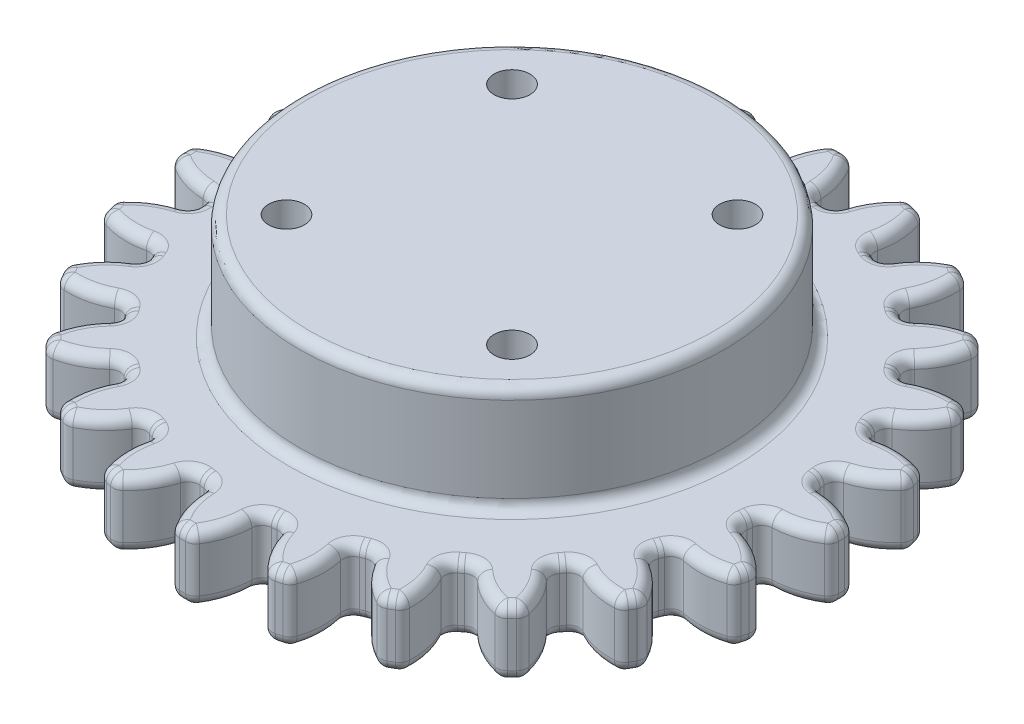
SolidWorks part; units mm, degrees
ref_plane "Front Plane" through (0, 0, 0) normal (0, 0, 1) x (1, 0, 0)
ref_plane "Top Plane" through (0, 0, 0) normal (0, 1, 0) x (1, 0, 0)
ref_plane "Right Plane" through (0, 0, 0) normal (1, 0, 0) x (0, 0, -1)
sketch "Sketch2" plane through (0, 0, 0) normal (0, 1, 0) x (1, 0, 0)
  line L0 (1.6066, 22.8619) -> (0, 0) construction
  line L1 (1.6066, 22.8619) -> (6.4656, 5.8944) construction
  line L2 (-1.8126, 20.7187) -> (0, 0) construction
  line L3 (0, 0) -> (1.8126, 20.7187) construction
  line L4 (-3.6115, 20.4818) -> (0, 0) construction
  line L5 (-6.4181, 23.9528) -> (0, 0) construction
  circle A0 centre (0, 0) radius 20.7978 construction
  circle A1 centre (0, 0) radius 24.7978 construction
  arc A2 (1.8126, 20.7187) -> (0.6469, 24.7894) centre (-4.078, 21.234) ccw
  arc A3 (-1.8126, 20.7187) -> (-0.6469, 24.7894) centre (4.078, 21.234) cw
  arc A4 (0.6469, 24.7894) -> (-0.6469, 24.7894) centre (0, 0) ccw
  arc A5 (1.8126, 20.7187) -> (3.6115, 20.4818) centre (0, 0) cw
  arc A6 (3.6115, 20.4818) -> (5.7911, 24.1121) centre (9.4348, 19.455) cw
  arc A7 (7.0408, 23.7772) -> (5.7911, 24.1121) centre (0, 0) ccw
  arc A8 (7.1133, 19.5435) -> (7.0408, 23.7772) centre (1.5567, 21.566) ccw
  arc A9 (7.1133, 19.5435) -> (8.7895, 18.8492) centre (0, 0) cw
  arc A10 (8.7895, 18.8492) -> (11.8344, 21.7917) centre (14.1487, 16.3502) cw
  arc A11 (12.9549, 21.1447) -> (11.8344, 21.7917) centre (0, 0) ccw
  arc A12 (11.9291, 17.0366) -> (12.9549, 21.1447) centre (7.0854, 20.4282) ccw
  arc A13 (11.9291, 17.0366) -> (13.3686, 15.932) centre (0, 0) cw
  arc A14 (13.3686, 15.932) -> (17.0713, 17.9862) centre (17.8983, 12.1311) cw
  arc A15 (17.9862, 17.0713) -> (17.0713, 17.9862) centre (0, 0) ccw
  arc A16 (15.932, 13.3686) -> (17.9862, 17.0713) centre (12.1311, 17.8983) ccw
  arc A17 (15.932, 13.3686) -> (17.0366, 11.9291) centre (0, 0) cw
  arc A18 (17.0366, 11.9291) -> (21.1447, 12.9549) centre (20.4282, 7.0854) cw
  arc A19 (21.7917, 11.8344) -> (21.1447, 12.9549) centre (0, 0) ccw
  arc A20 (18.8492, 8.7895) -> (21.7917, 11.8344) centre (16.3502, 14.1487) ccw
  arc A21 (18.8492, 8.7895) -> (19.5435, 7.1133) centre (0, 0) cw
  arc A22 (19.5435, 7.1133) -> (23.7772, 7.0408) centre (21.566, 1.5567) cw
  arc A23 (24.1121, 5.7911) -> (23.7772, 7.0408) centre (0, 0) ccw
  arc A24 (20.4818, 3.6115) -> (24.1121, 5.7911) centre (19.455, 9.4348) ccw
  arc A25 (20.4818, 3.6115) -> (20.7187, 1.8126) centre (0, 0) cw
  arc A26 (20.7187, 1.8126) -> (24.7894, 0.6469) centre (21.234, -4.078) cw
  arc A27 (24.7894, -0.6469) -> (24.7894, 0.6469) centre (0, 0) ccw
  arc A28 (20.7187, -1.8126) -> (24.7894, -0.6469) centre (21.234, 4.078) ccw
  arc A29 (20.7187, -1.8126) -> (20.4818, -3.6115) centre (0, 0) cw
  arc A30 (20.4818, -3.6115) -> (24.1121, -5.7911) centre (19.455, -9.4348) cw
  arc A31 (23.7772, -7.0408) -> (24.1121, -5.7911) centre (0, 0) ccw
  arc A32 (19.5435, -7.1133) -> (23.7772, -7.0408) centre (21.566, -1.5567) ccw
  arc A33 (19.5435, -7.1133) -> (18.8492, -8.7895) centre (0, 0) cw
  arc A34 (18.8492, -8.7895) -> (21.7917, -11.8344) centre (16.3502, -14.1487) cw
  arc A35 (21.1447, -12.9549) -> (21.7917, -11.8344) centre (0, 0) ccw
  arc A36 (17.0366, -11.9291) -> (21.1447, -12.9549) centre (20.4282, -7.0854) ccw
  arc A37 (17.0366, -11.9291) -> (15.932, -13.3686) centre (0, 0) cw
  arc A38 (15.932, -13.3686) -> (17.9862, -17.0713) centre (12.1311, -17.8983) cw
  arc A39 (17.0713, -17.9862) -> (17.9862, -17.0713) centre (0, 0) ccw
  arc A40 (13.3686, -15.932) -> (17.0713, -17.9862) centre (17.8983, -12.1311) ccw
  arc A41 (13.3686, -15.932) -> (11.9291, -17.0366) centre (0, 0) cw
  arc A42 (11.9291, -17.0366) -> (12.9549, -21.1447) centre (7.0854, -20.4282) cw
  arc A43 (11.8344, -21.7917) -> (12.9549, -21.1447) centre (0, 0) ccw
  arc A44 (8.7895, -18.8492) -> (11.8344, -21.7917) centre (14.1487, -16.3502) ccw
  arc A45 (8.7895, -18.8492) -> (7.1133, -19.5435) centre (0, 0) cw
  arc A46 (7.1133, -19.5435) -> (7.0408, -23.7772) centre (1.5567, -21.566) cw
  arc A47 (5.7911, -24.1121) -> (7.0408, -23.7772) centre (0, 0) ccw
  arc A48 (3.6115, -20.4818) -> (5.7911, -24.1121) centre (9.4348, -19.455) ccw
  arc A49 (3.6115, -20.4818) -> (1.8126, -20.7187) centre (0, 0) cw
  arc A50 (1.8126, -20.7187) -> (0.6469, -24.7894) centre (-4.078, -21.234) cw
  arc A51 (-0.6469, -24.7894) -> (0.6469, -24.7894) centre (0, 0) ccw
  arc A52 (-1.8126, -20.7187) -> (-0.6469, -24.7894) centre (4.078, -21.234) ccw
  arc A53 (-1.8126, -20.7187) -> (-3.6115, -20.4818) centre (0, 0) cw
  arc A54 (-3.6115, -20.4818) -> (-5.7911, -24.1121) centre (-9.4348, -19.455) cw
  arc A55 (-7.0408, -23.7772) -> (-5.7911, -24.1121) centre (0, 0) ccw
  arc A56 (-7.1133, -19.5435) -> (-7.0408, -23.7772) centre (-1.5567, -21.566) ccw
  arc A57 (-7.1133, -19.5435) -> (-8.7895, -18.8492) centre (0, 0) cw
  arc A58 (-8.7895, -18.8492) -> (-11.8344, -21.7917) centre (-14.1487, -16.3502) cw
  arc A59 (-12.9549, -21.1447) -> (-11.8344, -21.7917) centre (0, 0) ccw
  arc A60 (-11.9291, -17.0366) -> (-12.9549, -21.1447) centre (-7.0854, -20.4282) ccw
  arc A61 (-11.9291, -17.0366) -> (-13.3686, -15.932) centre (0, 0) cw
  arc A62 (-13.3686, -15.932) -> (-17.0713, -17.9862) centre (-17.8983, -12.1311) cw
  arc A63 (-17.9862, -17.0713) -> (-17.0713, -17.9862) centre (0, 0) ccw
  arc A64 (-15.932, -13.3686) -> (-17.9862, -17.0713) centre (-12.1311, -17.8983) ccw
  arc A65 (-15.932, -13.3686) -> (-17.0366, -11.9291) centre (0, 0) cw
  arc A66 (-17.0366, -11.9291) -> (-21.1447, -12.9549) centre (-20.4282, -7.0854) cw
  arc A67 (-21.7917, -11.8344) -> (-21.1447, -12.9549) centre (0, 0) ccw
  arc A68 (-18.8492, -8.7895) -> (-21.7917, -11.8344) centre (-16.3502, -14.1487) ccw
  arc A69 (-18.8492, -8.7895) -> (-19.5435, -7.1133) centre (0, 0) cw
  arc A70 (-19.5435, -7.1133) -> (-23.7772, -7.0408) centre (-21.566, -1.5567) cw
  arc A71 (-24.1121, -5.7911) -> (-23.7772, -7.0408) centre (0, 0) ccw
  arc A72 (-20.4818, -3.6115) -> (-24.1121, -5.7911) centre (-19.455, -9.4348) ccw
  arc A73 (-20.4818, -3.6115) -> (-20.7187, -1.8126) centre (0, 0) cw
  arc A74 (-20.7187, -1.8126) -> (-24.7894, -0.6469) centre (-21.234, 4.078) cw
  arc A75 (-24.7894, 0.6469) -> (-24.7894, -0.6469) centre (0, 0) ccw
  arc A76 (-20.7187, 1.8126) -> (-24.7894, 0.6469) centre (-21.234, -4.078) ccw
  arc A77 (-20.7187, 1.8126) -> (-20.4818, 3.6115) centre (0, 0) cw
  arc A78 (-20.4818, 3.6115) -> (-24.1121, 5.7911) centre (-19.455, 9.4348) cw
  arc A79 (-23.7772, 7.0408) -> (-24.1121, 5.7911) centre (0, 0) ccw
  arc A80 (-19.5435, 7.1133) -> (-23.7772, 7.0408) centre (-21.566, 1.5567) ccw
  arc A81 (-19.5435, 7.1133) -> (-18.8492, 8.7895) centre (0, 0) cw
  arc A82 (-18.8492, 8.7895) -> (-21.7917, 11.8344) centre (-16.3502, 14.1487) cw
  arc A83 (-21.1447, 12.9549) -> (-21.7917, 11.8344) centre (0, 0) ccw
  arc A84 (-17.0366, 11.9291) -> (-21.1447, 12.9549) centre (-20.4282, 7.0854) ccw
  arc A85 (-17.0366, 11.9291) -> (-15.932, 13.3686) centre (0, 0) cw
  arc A86 (-15.932, 13.3686) -> (-17.9862, 17.0713) centre (-12.1311, 17.8983) cw
  arc A87 (-17.0713, 17.9862) -> (-17.9862, 17.0713) centre (0, 0) ccw
  arc A88 (-13.3686, 15.932) -> (-17.0713, 17.9862) centre (-17.8983, 12.1311) ccw
  arc A89 (-13.3686, 15.932) -> (-11.9291, 17.0366) centre (0, 0) cw
  arc A90 (-11.9291, 17.0366) -> (-12.9549, 21.1447) centre (-7.0854, 20.4282) cw
  arc A91 (-11.8344, 21.7917) -> (-12.9549, 21.1447) centre (0, 0) ccw
  arc A92 (-8.7895, 18.8492) -> (-11.8344, 21.7917) centre (-14.1487, 16.3502) ccw
  arc A93 (-8.7895, 18.8492) -> (-7.1133, 19.5435) centre (0, 0) cw
  arc A94 (-7.1133, 19.5435) -> (-7.0408, 23.7772) centre (-1.5567, 21.566) cw
  arc A95 (-5.7911, 24.1121) -> (-7.0408, 23.7772) centre (0, 0) ccw
  arc A96 (-3.6115, 20.4818) -> (-5.7911, 24.1121) centre (-9.4348, 19.455) ccw
  arc A97 (-3.6115, 20.4818) -> (-1.8126, 20.7187) centre (0, 0) cw
  arc A98 (7.469, 21.6671) -> (1.6066, 22.8619) centre (0, 0) ccw construction
  arc A99 (-3.2334, 18.3373) -> (-4.8193, 17.9857) centre (0, 0) ccw
  arc A100 (-1.6229, 18.5494) -> (-3.2334, 18.3373) centre (0, 0) ccw
  point P12 (0, 24.7978)
  point P180 (0, 0)
  dimension "D2" = 4
  dimension "D1" = 20
  dimension "D4" = 6
  dimension "D3" = 24
extrude "Boss-Extrude1" add sketch "Sketch2" along normal blind 5 contours A8 A98 A6 A5 A2 A4 A3 A97 A96 A95 A94 A93 A92 A91 A90 A89 A88 A87 A86 A85 A84 A83 A82 A81 A80 A79 A78 A77 A76 A75 A74 A73 A72 A71 A70 A69 A68 A67 A66 A65 A64 A63 A62 A61 A60 A59 A58 A57 A56 A55 region at (0, 0, 0)
sketch "Sketch4" plane through (0, 5, 0) normal (0, 1, 0) x (1, 0, 0)
  circle A1 centre (0, 0) radius 16
  dimension "D1" = 32
extrude "Boss-Extrude2" add sketch "Sketch4" along normal blind 8
sketch "Sketch5" plane through (0, 0, 0) normal (0, -1, 0) x (1, 0, 0)
  circle A0 centre (0, 0) radius 13.1
  dimension "D1" = 26.2
extrude "Cut-Extrude1" cut sketch "Sketch5" against normal blind 5
fillet "Fillet2" radius 0.8 291 edges at (-3.6115, 2.5, -20.4818) (-5.7911, 2.5, -24.1121) (-7.0408, 2.5, -23.7772) (-7.1133, 2.5, -19.5435) (-8.7895, 2.5, -18.8492) (-11.8344, 2.5, -21.7917) (-12.9549, 2.5, -21.1447) (-11.9291, 2.5, -17.0366) (-13.3686, 2.5, -15.932) (-17.0713, 2.5, -17.9862) (-17.9862, 2.5, -17.0713) (-15.932, 2.5, -13.3686) (-17.0366, 2.5, -11.9291) (-21.1447, 2.5, -12.9549) (-21.7917, 2.5, -11.8344) (-18.8492, 2.5, -8.7895) (-19.5435, 2.5, -7.1133) (-23.7772, 2.5, -7.0408) (-24.1121, 2.5, -5.7911) (-20.4818, 2.5, -3.6115) (-20.7187, 2.5, -1.8126) (-24.7894, 2.5, -0.6469) (-24.7894, 2.5, 0.6469) (-20.7187, 2.5, 1.8126) (-20.4818, 2.5, 3.6115) (-24.1121, 2.5, 5.7911) (-23.7772, 2.5, 7.0408) (-19.5435, 2.5, 7.1133) (-18.8492, 2.5, 8.7895) (-21.7917, 2.5, 11.8344) (-21.1447, 2.5, 12.9549) (-17.0366, 2.5, 11.9291) (-15.932, 2.5, 13.3686) (-17.9862, 2.5, 17.0713) (-17.0713, 2.5, 17.9862) (-13.3686, 2.5, 15.932) (-11.9291, 2.5, 17.0366) (-12.9549, 2.5, 21.1447) (-11.8344, 2.5, 21.7917) (-8.7895, 2.5, 18.8492) (-7.1133, 2.5, 19.5435) (-7.0408, 2.5, 23.7772) (-5.7911, 2.5, 24.1121) (-3.6115, 2.5, 20.4818) (-1.8126, 2.5, 20.7187) (-0.6469, 2.5, 24.7894) (0.6469, 2.5, 24.7894) (1.8126, 2.5, 20.7187) (3.6115, 2.5, 20.4818) (5.7911, 2.5, 24.1121) (7.0408, 2.5, 23.7772) (7.1133, 2.5, 19.5435) (8.7895, 2.5, 18.8492) (11.8344, 2.5, 21.7917) (12.9549, 2.5, 21.1447) (11.9291, 2.5, 17.0366) (13.3686, 2.5, 15.932) (17.0713, 2.5, 17.9862) (17.9862, 2.5, 17.0713) (15.932, 2.5, 13.3686) (17.0366, 2.5, 11.9291) (21.1447, 2.5, 12.9549) (21.7917, 2.5, 11.8344) (18.8492, 2.5, 8.7895) (19.5435, 2.5, 7.1133) (23.7772, 2.5, 7.0408) (24.1121, 2.5, 5.7911) (20.4818, 2.5, 3.6115) (20.7187, 2.5, 1.8126) (24.7894, 2.5, 0.6469) (24.7894, 2.5, -0.6469) (20.7187, 2.5, -1.8126) (20.4818, 2.5, -3.6115) (24.1121, 2.5, -5.7911) (23.7772, 2.5, -7.0408) (19.5435, 2.5, -7.1133) (18.8492, 2.5, -8.7895) (21.7917, 2.5, -11.8344) (21.1447, 2.5, -12.9549) (17.0366, 2.5, -11.9291) (15.932, 2.5, -13.3686) (17.9862, 2.5, -17.0713) (17.0713, 2.5, -17.9862) (13.3686, 2.5, -15.932) (11.9291, 2.5, -17.0366) (12.9549, 2.5, -21.1447) (11.8344, 2.5, -21.7917) (8.7895, 2.5, -18.8492) (7.1133, 2.5, -19.5435) (7.0408, 2.5, -23.7772) (5.7911, 2.5, -24.1121) (3.6115, 2.5, -20.4818) (1.8126, 2.5, -20.7187) (0.6469, 2.5, -24.7894) (-0.6469, 2.5, -24.7894) (-1.8126, 2.5, -20.7187) (-1.6066, 5, -22.8619) (0, 5, -24.7978) (1.6066, 5, -22.8619) (2.7147, 5, -20.6199) (4.3652, 5, -22.4988) (6.4181, 5, -23.9528) (7.469, 5, -21.6671) (7.959, 5, -19.2147) (10.0396, 5, -20.6023) (12.3989, 5, -21.4755) (12.8224, 5, -18.9957) (12.6609, 5, -16.5) (15.0298, 5, -17.3019) (17.5347, 5, -17.5347) (17.3019, 5, -15.0298) (16.5, 5, -12.6609) (18.9957, 5, -12.8224) (21.4755, 5, -12.3989) (20.6023, 5, -10.0396) (19.2147, 5, -7.959) (21.6671, 5, -7.469) (23.9528, 5, -6.4181) (22.4988, 5, -4.3652) (20.6199, 5, -2.7147) (22.8619, 5, -1.6066) (24.7978, 5, 0) (22.8619, 5, 1.6066) (20.6199, 5, 2.7147) (22.4988, 5, 4.3652) (23.9528, 5, 6.4181) (21.6671, 5, 7.469) (19.2147, 5, 7.959) (20.6023, 5, 10.0396) (21.4755, 5, 12.3989) (18.9957, 5, 12.8224) (16.5, 5, 12.6609) (17.3019, 5, 15.0298) (17.5347, 5, 17.5347) (15.0298, 5, 17.3019) (12.6609, 5, 16.5) (12.8224, 5, 18.9957) (12.3989, 5, 21.4755) (10.0396, 5, 20.6023) (7.959, 5, 19.2147) (7.469, 5, 21.6671) (6.4181, 5, 23.9528) (4.3652, 5, 22.4988) (2.7147, 5, 20.6199) (1.6066, 5, 22.8619) (0, 5, 24.7978) (-1.6066, 5, 22.8619) (-2.7147, 5, 20.6199) (-4.3652, 5, 22.4988) (-6.4181, 5, 23.9528) (-7.469, 5, 21.6671) (-7.959, 5, 19.2147) (-10.0396, 5, 20.6023) (-12.3989, 5, 21.4755) (-12.8224, 5, 18.9957) (-12.6609, 5, 16.5) (-15.0298, 5, 17.3019) (-17.5347, 5, 17.5347) (-17.3019, 5, 15.0298) (-16.5, 5, 12.6609) (-18.9957, 5, 12.8224) (-21.4755, 5, 12.3989) (-20.6023, 5, 10.0396) (-19.2147, 5, 7.959) (-21.6671, 5, 7.469) (-23.9528, 5, 6.4181) (-22.4988, 5, 4.3652) (-20.6199, 5, 2.7147) (-22.8619, 5, 1.6066) (-24.7978, 5, 0) (-22.8619, 5, -1.6066) (-20.6199, 5, -2.7147) (-22.4988, 5, -4.3652) (-23.9528, 5, -6.4181) (-21.6671, 5, -7.469) (-19.2147, 5, -7.959) (-20.6023, 5, -10.0396) (-21.4755, 5, -12.3989) (-18.9957, 5, -12.8224) (-16.5, 5, -12.6609) (-17.3019, 5, -15.0298) (-17.5347, 5, -17.5347) (-15.0298, 5, -17.3019) (-12.6609, 5, -16.5) (-12.8224, 5, -18.9957) (-12.3989, 5, -21.4755) (-10.0396, 5, -20.6023) (-7.959, 5, -19.2147) (-7.469, 5, -21.6671) (-6.4181, 5, -23.9528) (-4.3652, 5, -22.4988) (-2.7147, 5, -20.6199) (-1.6066, 0, -22.8619) (0, 0, -24.7978) (1.6066, 0, -22.8619) (2.7147, 0, -20.6199) (4.3652, 0, -22.4988) (6.4181, 0, -23.9528) (7.469, 0, -21.6671) (7.959, 0, -19.2147) (10.0396, 0, -20.6023) (12.3989, 0, -21.4755) (12.8224, 0, -18.9957) (12.6609, 0, -16.5) (15.0298, 0, -17.3019) (17.5347, 0, -17.5347) (17.3019, 0, -15.0298) (16.5, 0, -12.6609) (18.9957, 0, -12.8224) (21.4755, 0, -12.3989) (20.6023, 0, -10.0396) (19.2147, 0, -7.959) (21.6671, 0, -7.469) (23.9528, 0, -6.4181) (22.4988, 0, -4.3652) (20.6199, 0, -2.7147) (22.8619, 0, -1.6066) (24.7978, 0, 0) (22.8619, 0, 1.6066) (20.6199, 0, 2.7147) (22.4988, 0, 4.3652) (23.9528, 0, 6.4181) (21.6671, 0, 7.469) (19.2147, 0, 7.959) (20.6023, 0, 10.0396) (21.4755, 0, 12.3989) (18.9957, 0, 12.8224) (16.5, 0, 12.6609) (17.3019, 0, 15.0298) (17.5347, 0, 17.5347) (15.0298, 0, 17.3019) (12.6609, 0, 16.5) (12.8224, 0, 18.9957) (12.3989, 0, 21.4755) (10.0396, 0, 20.6023) (7.959, 0, 19.2147) (7.469, 0, 21.6671) (6.4181, 0, 23.9528) (4.3652, 0, 22.4988) (2.7147, 0, 20.6199) (1.6066, 0, 22.8619) (0, 0, 24.7978) (-1.6066, 0, 22.8619) (-2.7147, 0, 20.6199) (-4.3652, 0, 22.4988) (-6.4181, 0, 23.9528) (-7.469, 0, 21.6671) (-7.959, 0, 19.2147) (-10.0396, 0, 20.6023) (-12.3989, 0, 21.4755) (-12.8224, 0, 18.9957) (-12.6609, 0, 16.5) (-15.0298, 0, 17.3019) (-17.5347, 0, 17.5347) (-17.3019, 0, 15.0298) (-16.5, 0, 12.6609) (-18.9957, 0, 12.8224) (-21.4755, 0, 12.3989) (-20.6023, 0, 10.0396) (-19.2147, 0, 7.959) (-21.6671, 0, 7.469) (-23.9528, 0, 6.4181) (-22.4988, 0, 4.3652) (-20.6199, 0, 2.7147) (-22.8619, 0, 1.6066) (-24.7978, 0, 0) (-22.8619, 0, -1.6066) (-20.6199, 0, -2.7147) (-22.4988, 0, -4.3652) (-23.9528, 0, -6.4181) (-21.6671, 0, -7.469) (-19.2147, 0, -7.959) (-20.6023, 0, -10.0396) (-21.4755, 0, -12.3989) (-18.9957, 0, -12.8224) (-16.5, 0, -12.6609) (-17.3019, 0, -15.0298) (-17.5347, 0, -17.5347) (-15.0298, 0, -17.3019) (-12.6609, 0, -16.5) (-12.8224, 0, -18.9957) (-12.3989, 0, -21.4755) (-10.0396, 0, -20.6023) (-7.959, 0, -19.2147) (-7.469, 0, -21.6671) (-6.4181, 0, -23.9528) (-4.3652, 0, -22.4988) (-2.7147, 0, -20.6199) (0, 5, 16) (0, 13, 16) (0, 0, -13.1)
sketch "Sketch6" plane through (0, 13, 0) normal (0, 1, 0) x (1, 0, 0)
  line L1 (-8.4853, -8.4853) -> (8.4853, -8.4853) construction
  line L2 (-8.4853, -8.4853) -> (-8.4853, 8.4853) construction
  line L3 (-8.4853, 8.4853) -> (8.4853, 8.4853) construction
  line L4 (8.4853, -8.4853) -> (8.4853, 8.4853) construction
  line L5 (-8.4853, -8.4853) -> (8.4853, 8.4853) construction
  line L6 (-8.4853, 8.4853) -> (8.4853, -8.4853) construction
  circle A0 centre (-8.4853, 8.4853) radius 1.35
  circle A1 centre (8.4853, 8.4853) radius 1.35
  circle A2 centre (8.4853, -8.4853) radius 1.35
  circle A3 centre (-8.4853, -8.4853) radius 1.35
  point P0 (0, 0)
  dimension "D2" = 2.7
  dimension "D1" = 24
extrude "Cut-Extrude2" cut sketch "Sketch6" against normal blind 7
